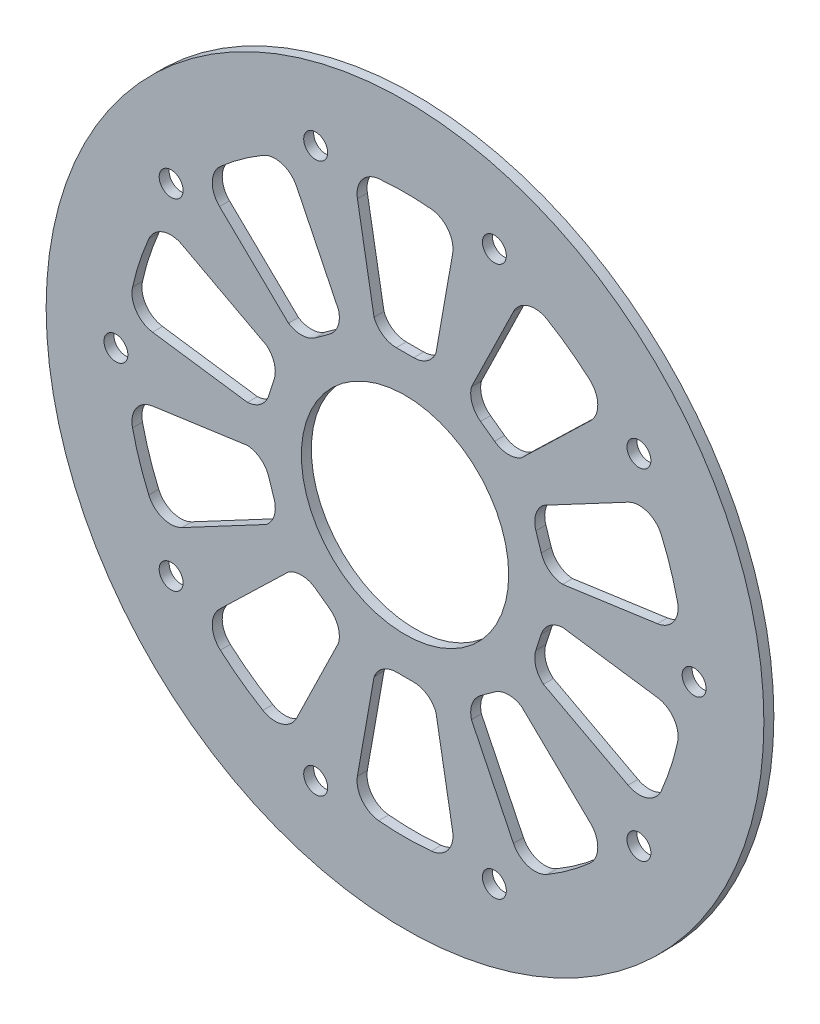
SolidWorks part; units mm, degrees
ref_plane "Ön Düzlem" through (0, 0, 0) normal (0, 0, 1) x (1, 0, 0)
ref_plane "Üst Düzlem" through (0, 0, 0) normal (0, 1, 0) x (1, 0, 0)
ref_plane "Sağ Düzlem" through (0, 0, 0) normal (1, 0, 0) x (0, 0, -1)
sketch "Model" plane through (0, 0, 0) normal (0, 0, 1) x (1, 0, 0)
  line L1 (60.5945, 121.4987) -> (60.8885, 121.3363)
  line L2 (60.8885, 121.3363) -> (61.139, 121.1124)
  line L3 (61.139, 121.1124) -> (61.3334, 120.8385)
  line L4 (61.3334, 120.8385) -> (61.4619, 120.5282)
  line L5 (61.4619, 120.5282) -> (61.5182, 120.197)
  line L6 (61.5182, 120.197) -> (61.4993, 119.8617)
  line L7 (61.4993, 119.8617) -> (61.4063, 119.5389)
  line L8 (61.4063, 119.5389) -> (45.7726, 92.4605)
  line L9 (45.7726, 92.4605) -> (42.0525, 92.3778)
  line L10 (42.0525, 92.3778) -> (41.4785, 90.992)
  line L11 (58.0621, 81.4174) -> (58.9753, 82.6074)
  line L12 (58.9753, 82.6074) -> (57.1868, 85.8705)
  line L13 (57.1868, 85.8705) -> (72.8206, 112.9489)
  line L14 (72.8206, 112.9489) -> (73.0536, 113.1908)
  line L15 (73.0536, 113.1908) -> (73.3346, 113.3748)
  line L16 (73.3346, 113.3748) -> (73.6495, 113.4917)
  line L17 (73.6495, 113.4917) -> (73.9825, 113.5355)
  line L18 (73.9825, 113.5355) -> (74.317, 113.5041)
  line L19 (74.317, 113.5041) -> (74.636, 113.3991)
  line L20 (74.636, 113.3991) -> (74.9237, 113.2258)
  line L21 (74.9237, 113.2258) -> (89.976, 101.6758)
  line L22 (89.976, 101.6758) -> (90.2179, 101.4427)
  line L23 (90.2179, 101.4427) -> (90.4019, 101.1617)
  line L24 (90.4019, 101.1617) -> (90.5188, 100.8468)
  line L25 (90.5188, 100.8468) -> (90.5626, 100.5138)
  line L26 (90.5626, 100.5138) -> (90.5313, 100.1793)
  line L27 (90.5313, 100.1793) -> (90.4263, 99.8603)
  line L28 (90.4263, 99.8603) -> (90.2529, 99.5726)
  line L29 (90.2529, 99.5726) -> (68.1435, 77.4631)
  line L30 (68.1435, 77.4631) -> (64.5287, 78.3461)
  line L31 (64.5287, 78.3461) -> (63.6156, 77.1561)
  line L32 (77.1561, 63.6156) -> (78.3461, 64.5287)
  line L33 (78.3461, 64.5287) -> (77.4631, 68.1435)
  line L34 (77.4631, 68.1435) -> (99.5726, 90.2529)
  line L35 (99.5726, 90.2529) -> (99.8603, 90.4263)
  line L36 (99.8603, 90.4263) -> (100.1793, 90.5313)
  line L37 (100.1793, 90.5313) -> (100.5138, 90.5626)
  line L38 (100.5138, 90.5626) -> (100.8468, 90.5188)
  line L39 (100.8468, 90.5188) -> (101.1617, 90.4019)
  line L40 (101.1617, 90.4019) -> (101.4427, 90.2179)
  line L41 (101.4427, 90.2179) -> (101.6758, 89.976)
  line L42 (101.6758, 89.976) -> (113.2258, 74.9237)
  line L43 (113.2258, 74.9237) -> (113.3991, 74.636)
  line L44 (113.3991, 74.636) -> (113.5041, 74.317)
  line L45 (113.5041, 74.317) -> (113.5355, 73.9825)
  line L46 (113.5355, 73.9825) -> (113.4917, 73.6495)
  line L47 (113.4917, 73.6495) -> (113.3748, 73.3346)
  line L48 (113.3748, 73.3346) -> (113.1908, 73.0536)
  line L49 (113.1908, 73.0536) -> (112.9489, 72.8206)
  line L50 (112.9489, 72.8206) -> (85.8705, 57.1868)
  line L51 (85.8705, 57.1868) -> (82.6074, 58.9753)
  line L52 (82.6074, 58.9753) -> (81.4174, 58.0621)
  line L53 (90.992, 41.4785) -> (92.3778, 42.0525)
  line L54 (92.3778, 42.0525) -> (92.4605, 45.7726)
  line L55 (92.4605, 45.7726) -> (119.5389, 61.4063)
  line L56 (119.5389, 61.4063) -> (119.8617, 61.4993)
  line L57 (119.8617, 61.4993) -> (120.197, 61.5182)
  line L58 (120.197, 61.5182) -> (120.5282, 61.4619)
  line L59 (120.5282, 61.4619) -> (120.8385, 61.3334)
  line L60 (120.8385, 61.3334) -> (121.1124, 61.139)
  line L61 (121.1124, 61.139) -> (121.3363, 60.8885)
  line L62 (121.3363, 60.8885) -> (121.4987, 60.5945)
  line L63 (121.4987, 60.5945) -> (128.7594, 43.0658)
  line L64 (128.7594, 43.0658) -> (128.8524, 42.743)
  line L65 (128.8524, 42.743) -> (128.8712, 42.4076)
  line L66 (128.8712, 42.4076) -> (128.815, 42.0765)
  line L67 (128.815, 42.0765) -> (128.6864, 41.7662)
  line L68 (128.6864, 41.7662) -> (128.492, 41.4922)
  line L69 (128.492, 41.4922) -> (128.2416, 41.2684)
  line L70 (128.2416, 41.2684) -> (127.9476, 41.1059)
  line L71 (127.9476, 41.1059) -> (97.7455, 33.0133)
  line L72 (97.7455, 33.0133) -> (95.0566, 35.5853)
  line L73 (95.0566, 35.5853) -> (93.6707, 35.0113)
  line L74 (98.6269, 16.5147) -> (100.1141, 16.7105)
  line L75 (100.1141, 16.7105) -> (101.1568, 20.2824)
  line L76 (101.1568, 20.2824) -> (131.3588, 28.375)
  line L77 (131.3588, 28.375) -> (131.6947, 28.3813)
  line L78 (131.6947, 28.3813) -> (132.0235, 28.3127)
  line L79 (132.0235, 28.3127) -> (132.3288, 28.1726)
  line L80 (132.3288, 28.1726) -> (132.5953, 27.9682)
  line L81 (132.5953, 27.9682) -> (132.8096, 27.7095)
  line L82 (132.8096, 27.7095) -> (132.9609, 27.4097)
  line L83 (132.9609, 27.4097) -> (133.0418, 27.0836)
  line L84 (133.0418, 27.0836) -> (135.5183, 8.273)
  line L85 (135.5183, 8.273) -> (135.5246, 7.9371)
  line L86 (135.5246, 7.9371) -> (135.4559, 7.6083)
  line L87 (135.4559, 7.6083) -> (135.3159, 7.303)
  line L88 (135.3159, 7.303) -> (135.1114, 7.0365)
  line L89 (135.1114, 7.0365) -> (134.8528, 6.8222)
  line L90 (134.8528, 6.8222) -> (134.5529, 6.6709)
  line L91 (134.5529, 6.6709) -> (134.2269, 6.59)
  line L92 (134.2269, 6.59) -> (102.9594, 6.59)
  line L93 (102.9594, 6.59) -> (101.0278, 9.7704)
  line L94 (101.0278, 9.7704) -> (99.5406, 9.5746)
  line L95 (99.5406, -9.5746) -> (101.0278, -9.7704)
  line L96 (101.0278, -9.7704) -> (102.9594, -6.59)
  line L97 (102.9594, -6.59) -> (134.2269, -6.59)
  line L98 (134.2269, -6.59) -> (134.5529, -6.6709)
  line L99 (134.5529, -6.6709) -> (134.8528, -6.8222)
  line L100 (134.8528, -6.8222) -> (135.1114, -7.0365)
  line L101 (135.1114, -7.0365) -> (135.3159, -7.303)
  line L102 (135.3159, -7.303) -> (135.4559, -7.6083)
  line L103 (135.4559, -7.6083) -> (135.5246, -7.9371)
  line L104 (135.5246, -7.9371) -> (135.5183, -8.273)
  line L105 (135.5183, -8.273) -> (133.0418, -27.0836)
  line L106 (133.0418, -27.0836) -> (132.9609, -27.4097)
  line L107 (132.9609, -27.4097) -> (132.8096, -27.7095)
  line L108 (132.8096, -27.7095) -> (132.5953, -27.9682)
  line L109 (132.5953, -27.9682) -> (132.3288, -28.1726)
  line L110 (132.3288, -28.1726) -> (132.0235, -28.3127)
  line L111 (132.0235, -28.3127) -> (131.6947, -28.3813)
  line L112 (131.6947, -28.3813) -> (131.3588, -28.375)
  line L113 (131.3588, -28.375) -> (101.1568, -20.2824)
  line L114 (101.1568, -20.2824) -> (100.1141, -16.7105)
  line L115 (100.1141, -16.7105) -> (98.6269, -16.5147)
  line L116 (93.6707, -35.0113) -> (95.0566, -35.5853)
  line L117 (95.0566, -35.5853) -> (97.7455, -33.0133)
  line L118 (97.7455, -33.0133) -> (127.9476, -41.1059)
  line L119 (127.9476, -41.1059) -> (128.2416, -41.2684)
  line L120 (128.2416, -41.2684) -> (128.492, -41.4922)
  line L121 (128.492, -41.4922) -> (128.6864, -41.7662)
  line L122 (128.6864, -41.7662) -> (128.815, -42.0765)
  line L123 (128.815, -42.0765) -> (128.8712, -42.4076)
  line L124 (128.8712, -42.4076) -> (128.8524, -42.743)
  line L125 (128.8524, -42.743) -> (128.7594, -43.0658)
  line L126 (128.7594, -43.0658) -> (121.4987, -60.5945)
  line L127 (121.4987, -60.5945) -> (121.3363, -60.8885)
  line L128 (121.3363, -60.8885) -> (121.1124, -61.139)
  line L129 (121.1124, -61.139) -> (120.8385, -61.3334)
  line L130 (120.8385, -61.3334) -> (120.5282, -61.4619)
  line L131 (120.5282, -61.4619) -> (120.197, -61.5182)
  line L132 (120.197, -61.5182) -> (119.8617, -61.4993)
  line L133 (119.8617, -61.4993) -> (119.5389, -61.4063)
  line L134 (119.5389, -61.4063) -> (92.4605, -45.7726)
  line L135 (92.4605, -45.7726) -> (92.3778, -42.0525)
  line L136 (92.3778, -42.0525) -> (90.992, -41.4785)
  line L137 (81.4174, -58.0621) -> (82.6074, -58.9753)
  line L138 (82.6074, -58.9753) -> (85.8705, -57.1868)
  line L139 (85.8705, -57.1868) -> (112.9489, -72.8206)
  line L140 (112.9489, -72.8206) -> (113.1908, -73.0536)
  line L141 (113.1908, -73.0536) -> (113.3748, -73.3346)
  line L142 (113.3748, -73.3346) -> (113.4917, -73.6495)
  line L143 (113.4917, -73.6495) -> (113.5355, -73.9825)
  line L144 (113.5355, -73.9825) -> (113.5041, -74.317)
  line L145 (113.5041, -74.317) -> (113.3991, -74.636)
  line L146 (113.3991, -74.636) -> (113.2258, -74.9237)
  line L147 (113.2258, -74.9237) -> (101.6758, -89.976)
  line L148 (101.6758, -89.976) -> (101.4427, -90.2179)
  line L149 (101.4427, -90.2179) -> (101.1617, -90.4019)
  line L150 (101.1617, -90.4019) -> (100.8468, -90.5188)
  line L151 (100.8468, -90.5188) -> (100.5138, -90.5626)
  line L152 (100.5138, -90.5626) -> (100.1793, -90.5313)
  line L153 (100.1793, -90.5313) -> (99.8603, -90.4263)
  line L154 (99.8603, -90.4263) -> (99.5726, -90.2529)
  line L155 (99.5726, -90.2529) -> (77.4631, -68.1435)
  line L156 (77.4631, -68.1435) -> (78.3461, -64.5287)
  line L157 (78.3461, -64.5287) -> (77.1561, -63.6156)
  line L158 (63.6156, -77.1561) -> (64.5287, -78.3461)
  line L159 (64.5287, -78.3461) -> (68.1435, -77.4631)
  line L160 (68.1435, -77.4631) -> (90.2529, -99.5726)
  line L161 (90.2529, -99.5726) -> (90.4263, -99.8603)
  line L162 (90.4263, -99.8603) -> (90.5313, -100.1793)
  line L163 (90.5313, -100.1793) -> (90.5626, -100.5138)
  line L164 (90.5626, -100.5138) -> (90.5188, -100.8468)
  line L165 (90.5188, -100.8468) -> (90.4019, -101.1617)
  line L166 (90.4019, -101.1617) -> (90.2179, -101.4427)
  line L167 (90.2179, -101.4427) -> (89.976, -101.6758)
  line L168 (89.976, -101.6758) -> (74.9237, -113.2258)
  line L169 (74.9237, -113.2258) -> (74.636, -113.3991)
  line L170 (74.636, -113.3991) -> (74.317, -113.5041)
  line L171 (74.317, -113.5041) -> (73.9825, -113.5355)
  line L172 (73.9825, -113.5355) -> (73.6495, -113.4917)
  line L173 (73.6495, -113.4917) -> (73.3346, -113.3748)
  line L174 (73.3346, -113.3748) -> (73.0536, -113.1908)
  line L175 (73.0536, -113.1908) -> (72.8206, -112.9489)
  line L176 (72.8206, -112.9489) -> (57.1868, -85.8705)
  line L177 (57.1868, -85.8705) -> (58.9753, -82.6074)
  line L178 (58.9753, -82.6074) -> (58.0621, -81.4174)
  line L179 (41.4785, -90.992) -> (42.0525, -92.3778)
  line L180 (42.0525, -92.3778) -> (45.7726, -92.4605)
  line L181 (45.7726, -92.4605) -> (61.4063, -119.5389)
  line L182 (61.4063, -119.5389) -> (61.4993, -119.8617)
  line L183 (61.4993, -119.8617) -> (61.5182, -120.197)
  line L184 (61.5182, -120.197) -> (61.4619, -120.5282)
  line L185 (61.4619, -120.5282) -> (61.3334, -120.8385)
  line L186 (61.3334, -120.8385) -> (61.139, -121.1124)
  line L187 (61.139, -121.1124) -> (60.8885, -121.3363)
  line L188 (60.8885, -121.3363) -> (60.5945, -121.4987)
  line L189 (60.5945, -121.4987) -> (43.0658, -128.7594)
  line L190 (43.0658, -128.7594) -> (42.743, -128.8524)
  line L191 (42.743, -128.8524) -> (42.4076, -128.8712)
  line L192 (42.4076, -128.8712) -> (42.0765, -128.815)
  line L193 (42.0765, -128.815) -> (41.7662, -128.6864)
  line L194 (41.7662, -128.6864) -> (41.4922, -128.492)
  line L195 (41.4922, -128.492) -> (41.2684, -128.2416)
  line L196 (41.2684, -128.2416) -> (41.1059, -127.9476)
  line L197 (41.1059, -127.9476) -> (33.0133, -97.7455)
  line L198 (33.0133, -97.7455) -> (35.5853, -95.0566)
  line L199 (35.5853, -95.0566) -> (35.0113, -93.6707)
  line L200 (16.5147, -98.6269) -> (16.7105, -100.1141)
  line L201 (16.7105, -100.1141) -> (20.2824, -101.1568)
  line L202 (20.2824, -101.1568) -> (28.375, -131.3588)
  line L203 (28.375, -131.3588) -> (28.3813, -131.6947)
  line L204 (28.3813, -131.6947) -> (28.3127, -132.0235)
  line L205 (28.3127, -132.0235) -> (28.1726, -132.3288)
  line L206 (28.1726, -132.3288) -> (27.9682, -132.5953)
  line L207 (27.9682, -132.5953) -> (27.7095, -132.8096)
  line L208 (27.7095, -132.8096) -> (27.4097, -132.9609)
  line L209 (27.4097, -132.9609) -> (27.0836, -133.0418)
  line L210 (27.0836, -133.0418) -> (8.273, -135.5183)
  line L211 (8.273, -135.5183) -> (7.9371, -135.5246)
  line L212 (7.9371, -135.5246) -> (7.6083, -135.4559)
  line L213 (7.6083, -135.4559) -> (7.303, -135.3159)
  line L214 (7.303, -135.3159) -> (7.0365, -135.1114)
  line L215 (7.0365, -135.1114) -> (6.8222, -134.8528)
  line L216 (6.8222, -134.8528) -> (6.6709, -134.5529)
  line L217 (6.6709, -134.5529) -> (6.59, -134.2269)
  line L218 (6.59, -134.2269) -> (6.59, -102.9594)
  line L219 (6.59, -102.9594) -> (9.7704, -101.0278)
  line L220 (9.7704, -101.0278) -> (9.5746, -99.5406)
  line L221 (-9.5746, -99.5406) -> (-9.7704, -101.0278)
  line L222 (-9.7704, -101.0278) -> (-6.59, -102.9594)
  line L223 (-6.59, -102.9594) -> (-6.59, -134.2269)
  line L224 (-6.59, -134.2269) -> (-6.6709, -134.5529)
  line L225 (-6.6709, -134.5529) -> (-6.8222, -134.8528)
  line L226 (-6.8222, -134.8528) -> (-7.0365, -135.1114)
  line L227 (-7.0365, -135.1114) -> (-7.303, -135.3159)
  line L228 (-7.303, -135.3159) -> (-7.6083, -135.4559)
  line L229 (-7.6083, -135.4559) -> (-7.9371, -135.5246)
  line L230 (-7.9371, -135.5246) -> (-8.273, -135.5183)
  line L231 (-8.273, -135.5183) -> (-27.0836, -133.0418)
  line L232 (-27.0836, -133.0418) -> (-27.4097, -132.9609)
  line L233 (-27.4097, -132.9609) -> (-27.7095, -132.8096)
  line L234 (-27.7095, -132.8096) -> (-27.9682, -132.5953)
  line L235 (-27.9682, -132.5953) -> (-28.1726, -132.3288)
  line L236 (-28.1726, -132.3288) -> (-28.3127, -132.0235)
  line L237 (-28.3127, -132.0235) -> (-28.3813, -131.6947)
  line L238 (-28.3813, -131.6947) -> (-28.375, -131.3588)
  line L239 (-28.375, -131.3588) -> (-20.2824, -101.1568)
  line L240 (-20.2824, -101.1568) -> (-16.7105, -100.1141)
  line L241 (-16.7105, -100.1141) -> (-16.5147, -98.6269)
  line L242 (-35.0113, -93.6707) -> (-35.5853, -95.0566)
  line L243 (-35.5853, -95.0566) -> (-33.0133, -97.7455)
  line L244 (-33.0133, -97.7455) -> (-41.1059, -127.9476)
  line L245 (-41.1059, -127.9476) -> (-41.2684, -128.2416)
  line L246 (-41.2684, -128.2416) -> (-41.4922, -128.492)
  line L247 (-41.4922, -128.492) -> (-41.7662, -128.6864)
  line L248 (-41.7662, -128.6864) -> (-42.0765, -128.815)
  line L249 (-42.0765, -128.815) -> (-42.4076, -128.8712)
  line L250 (-42.4076, -128.8712) -> (-42.743, -128.8524)
  line L251 (-42.743, -128.8524) -> (-43.0658, -128.7594)
  line L252 (-43.0658, -128.7594) -> (-60.5945, -121.4987)
  line L253 (-60.5945, -121.4987) -> (-60.8885, -121.3363)
  line L254 (-60.8885, -121.3363) -> (-61.139, -121.1124)
  line L255 (-61.139, -121.1124) -> (-61.3334, -120.8385)
  line L256 (-61.3334, -120.8385) -> (-61.4619, -120.5282)
  line L257 (-61.4619, -120.5282) -> (-61.5182, -120.197)
  line L258 (-61.5182, -120.197) -> (-61.4993, -119.8617)
  line L259 (-61.4993, -119.8617) -> (-61.4063, -119.5389)
  line L260 (-61.4063, -119.5389) -> (-45.7726, -92.4605)
  line L261 (-45.7726, -92.4605) -> (-42.0525, -92.3778)
  line L262 (-42.0525, -92.3778) -> (-41.4785, -90.992)
  line L263 (-58.0621, -81.4174) -> (-58.9753, -82.6074)
  line L264 (-58.9753, -82.6074) -> (-57.1868, -85.8705)
  line L265 (-57.1868, -85.8705) -> (-72.8206, -112.9489)
  line L266 (-72.8206, -112.9489) -> (-73.0536, -113.1908)
  line L267 (-73.0536, -113.1908) -> (-73.3346, -113.3748)
  line L268 (-73.3346, -113.3748) -> (-73.6495, -113.4917)
  line L269 (-73.6495, -113.4917) -> (-73.9825, -113.5355)
  line L270 (-73.9825, -113.5355) -> (-74.317, -113.5041)
  line L271 (-74.317, -113.5041) -> (-74.636, -113.3991)
  line L272 (-74.636, -113.3991) -> (-74.9237, -113.2258)
  line L273 (-74.9237, -113.2258) -> (-89.976, -101.6758)
  line L274 (-89.976, -101.6758) -> (-90.2179, -101.4427)
  line L275 (-90.2179, -101.4427) -> (-90.4019, -101.1617)
  line L276 (-90.4019, -101.1617) -> (-90.5188, -100.8468)
  line L277 (-90.5188, -100.8468) -> (-90.5626, -100.5138)
  line L278 (-90.5626, -100.5138) -> (-90.5313, -100.1793)
  line L279 (-90.5313, -100.1793) -> (-90.4263, -99.8603)
  line L280 (-90.4263, -99.8603) -> (-90.2529, -99.5726)
  line L281 (-90.2529, -99.5726) -> (-68.1435, -77.4631)
  line L282 (-68.1435, -77.4631) -> (-64.5287, -78.3461)
  line L283 (-64.5287, -78.3461) -> (-63.6156, -77.1561)
  line L284 (-77.1561, -63.6156) -> (-78.3461, -64.5287)
  line L285 (-78.3461, -64.5287) -> (-77.4631, -68.1435)
  line L286 (-77.4631, -68.1435) -> (-99.5726, -90.2529)
  line L287 (-99.5726, -90.2529) -> (-99.8603, -90.4263)
  line L288 (-99.8603, -90.4263) -> (-100.1793, -90.5313)
  line L289 (-100.1793, -90.5313) -> (-100.5138, -90.5626)
  line L290 (-100.5138, -90.5626) -> (-100.8468, -90.5188)
  line L291 (-100.8468, -90.5188) -> (-101.1617, -90.4019)
  line L292 (-101.1617, -90.4019) -> (-101.4427, -90.2179)
  line L293 (-101.4427, -90.2179) -> (-101.6758, -89.976)
  line L294 (-101.6758, -89.976) -> (-113.2258, -74.9237)
  line L295 (-113.2258, -74.9237) -> (-113.3991, -74.636)
  line L296 (-113.3991, -74.636) -> (-113.5041, -74.317)
  line L297 (-113.5041, -74.317) -> (-113.5355, -73.9825)
  line L298 (-113.5355, -73.9825) -> (-113.4917, -73.6495)
  line L299 (-113.4917, -73.6495) -> (-113.3748, -73.3346)
  line L300 (-113.3748, -73.3346) -> (-113.1908, -73.0536)
  line L301 (-113.1908, -73.0536) -> (-112.9489, -72.8206)
  line L302 (-112.9489, -72.8206) -> (-85.8705, -57.1868)
  line L303 (-85.8705, -57.1868) -> (-82.6074, -58.9753)
  line L304 (-82.6074, -58.9753) -> (-81.4174, -58.0621)
  line L305 (-90.992, -41.4785) -> (-92.3778, -42.0525)
  line L306 (-92.3778, -42.0525) -> (-92.4605, -45.7726)
  line L307 (-92.4605, -45.7726) -> (-119.5389, -61.4063)
  line L308 (-119.5389, -61.4063) -> (-119.8617, -61.4993)
  line L309 (-119.8617, -61.4993) -> (-120.197, -61.5182)
  line L310 (-120.197, -61.5182) -> (-120.5282, -61.4619)
  line L311 (-120.5282, -61.4619) -> (-120.8385, -61.3334)
  line L312 (-120.8385, -61.3334) -> (-121.1124, -61.139)
  line L313 (-121.1124, -61.139) -> (-121.3363, -60.8885)
  line L314 (-121.3363, -60.8885) -> (-121.4987, -60.5945)
  line L315 (-121.4987, -60.5945) -> (-128.7594, -43.0658)
  line L316 (-128.7594, -43.0658) -> (-128.8524, -42.743)
  line L317 (-128.8524, -42.743) -> (-128.8712, -42.4076)
  line L318 (-128.8712, -42.4076) -> (-128.815, -42.0765)
  line L319 (-128.815, -42.0765) -> (-128.6864, -41.7662)
  line L320 (-128.6864, -41.7662) -> (-128.492, -41.4922)
  line L321 (-128.492, -41.4922) -> (-128.2416, -41.2684)
  line L322 (-128.2416, -41.2684) -> (-127.9476, -41.1059)
  line L323 (-127.9476, -41.1059) -> (-97.7455, -33.0133)
  line L324 (-97.7455, -33.0133) -> (-95.0566, -35.5853)
  line L325 (-95.0566, -35.5853) -> (-93.6707, -35.0113)
  line L326 (-98.6269, -16.5147) -> (-100.1141, -16.7105)
  line L327 (-100.1141, -16.7105) -> (-101.1568, -20.2824)
  line L328 (-101.1568, -20.2824) -> (-131.3588, -28.375)
  line L329 (-131.3588, -28.375) -> (-131.6947, -28.3813)
  line L330 (-131.6947, -28.3813) -> (-132.0235, -28.3127)
  line L331 (-132.0235, -28.3127) -> (-132.3288, -28.1726)
  line L332 (-132.3288, -28.1726) -> (-132.5953, -27.9682)
  line L333 (-132.5953, -27.9682) -> (-132.8096, -27.7095)
  line L334 (-132.8096, -27.7095) -> (-132.9609, -27.4097)
  line L335 (-132.9609, -27.4097) -> (-133.0418, -27.0836)
  line L336 (-133.0418, -27.0836) -> (-135.5183, -8.273)
  line L337 (-135.5183, -8.273) -> (-135.5246, -7.9371)
  line L338 (-135.5246, -7.9371) -> (-135.4559, -7.6083)
  line L339 (-135.4559, -7.6083) -> (-135.3159, -7.303)
  line L340 (-135.3159, -7.303) -> (-135.1114, -7.0365)
  line L341 (-135.1114, -7.0365) -> (-134.8528, -6.8222)
  line L342 (-134.8528, -6.8222) -> (-134.5529, -6.6709)
  line L343 (-134.5529, -6.6709) -> (-134.2269, -6.59)
  line L344 (-134.2269, -6.59) -> (-102.9594, -6.59)
  line L345 (-102.9594, -6.59) -> (-101.0278, -9.7704)
  line L346 (-101.0278, -9.7704) -> (-99.5406, -9.5746)
  line L347 (-99.5406, 9.5746) -> (-101.0278, 9.7704)
  line L348 (-101.0278, 9.7704) -> (-102.9594, 6.59)
  line L349 (-102.9594, 6.59) -> (-134.2269, 6.59)
  line L350 (-134.2269, 6.59) -> (-134.5529, 6.6709)
  line L351 (-134.5529, 6.6709) -> (-134.8528, 6.8222)
  line L352 (-134.8528, 6.8222) -> (-135.1114, 7.0365)
  line L353 (-135.1114, 7.0365) -> (-135.3159, 7.303)
  line L354 (-135.3159, 7.303) -> (-135.4559, 7.6083)
  line L355 (-135.4559, 7.6083) -> (-135.5246, 7.9371)
  line L356 (-135.5246, 7.9371) -> (-135.5183, 8.273)
  line L357 (-135.5183, 8.273) -> (-133.0418, 27.0836)
  line L358 (-133.0418, 27.0836) -> (-132.9609, 27.4097)
  line L359 (-132.9609, 27.4097) -> (-132.8096, 27.7095)
  line L360 (-132.8096, 27.7095) -> (-132.5953, 27.9682)
  line L361 (-132.5953, 27.9682) -> (-132.3288, 28.1726)
  line L362 (-132.3288, 28.1726) -> (-132.0235, 28.3127)
  line L363 (-132.0235, 28.3127) -> (-131.6947, 28.3813)
  line L364 (-131.6947, 28.3813) -> (-131.3588, 28.375)
  line L365 (-131.3588, 28.375) -> (-101.1568, 20.2824)
  line L366 (-101.1568, 20.2824) -> (-100.1141, 16.7105)
  line L367 (-100.1141, 16.7105) -> (-98.6269, 16.5147)
  line L368 (-93.6707, 35.0113) -> (-95.0566, 35.5853)
  line L369 (-95.0566, 35.5853) -> (-97.7455, 33.0133)
  line L370 (-97.7455, 33.0133) -> (-127.9476, 41.1059)
  line L371 (-127.9476, 41.1059) -> (-128.2416, 41.2684)
  line L372 (-128.2416, 41.2684) -> (-128.492, 41.4922)
  line L373 (-128.492, 41.4922) -> (-128.6864, 41.7662)
  line L374 (-128.6864, 41.7662) -> (-128.815, 42.0765)
  line L375 (-128.815, 42.0765) -> (-128.8712, 42.4076)
  line L376 (-128.8712, 42.4076) -> (-128.8524, 42.743)
  line L377 (-128.8524, 42.743) -> (-128.7594, 43.0658)
  line L378 (-128.7594, 43.0658) -> (-121.4987, 60.5945)
  line L379 (-121.4987, 60.5945) -> (-121.3363, 60.8885)
  line L380 (-121.3363, 60.8885) -> (-121.1124, 61.139)
  line L381 (-121.1124, 61.139) -> (-120.8385, 61.3334)
  line L382 (-120.8385, 61.3334) -> (-120.5282, 61.4619)
  line L383 (-120.5282, 61.4619) -> (-120.197, 61.5182)
  line L384 (-120.197, 61.5182) -> (-119.8617, 61.4993)
  line L385 (-119.8617, 61.4993) -> (-119.5389, 61.4063)
  line L386 (-119.5389, 61.4063) -> (-92.4605, 45.7726)
  line L387 (-92.4605, 45.7726) -> (-92.3778, 42.0525)
  line L388 (-92.3778, 42.0525) -> (-90.992, 41.4785)
  line L389 (-81.4174, 58.0621) -> (-82.6074, 58.9753)
  line L390 (-82.6074, 58.9753) -> (-85.8705, 57.1868)
  line L391 (-85.8705, 57.1868) -> (-112.9489, 72.8206)
  line L392 (-112.9489, 72.8206) -> (-113.1908, 73.0536)
  line L393 (-113.1908, 73.0536) -> (-113.3748, 73.3346)
  line L394 (-113.3748, 73.3346) -> (-113.4917, 73.6495)
  line L395 (-113.4917, 73.6495) -> (-113.5355, 73.9825)
  line L396 (-113.5355, 73.9825) -> (-113.5041, 74.317)
  line L397 (-113.5041, 74.317) -> (-113.3991, 74.636)
  line L398 (-113.3991, 74.636) -> (-113.2258, 74.9237)
  line L399 (-113.2258, 74.9237) -> (-101.6758, 89.976)
  line L400 (-101.6758, 89.976) -> (-101.4427, 90.2179)
  line L401 (-101.4427, 90.2179) -> (-101.1617, 90.4019)
  line L402 (-101.1617, 90.4019) -> (-100.8468, 90.5188)
  line L403 (-100.8468, 90.5188) -> (-100.5138, 90.5626)
  line L404 (-100.5138, 90.5626) -> (-100.1793, 90.5313)
  line L405 (-100.1793, 90.5313) -> (-99.8603, 90.4263)
  line L406 (-99.8603, 90.4263) -> (-99.5726, 90.2529)
  line L407 (-99.5726, 90.2529) -> (-77.4631, 68.1435)
  line L408 (-77.4631, 68.1435) -> (-78.3461, 64.5287)
  line L409 (-78.3461, 64.5287) -> (-77.1561, 63.6156)
  line L410 (-63.6156, 77.1561) -> (-64.5287, 78.3461)
  line L411 (-64.5287, 78.3461) -> (-68.1435, 77.4631)
  line L412 (-68.1435, 77.4631) -> (-90.2529, 99.5726)
  line L413 (-90.2529, 99.5726) -> (-90.4263, 99.8603)
  line L414 (-90.4263, 99.8603) -> (-90.5313, 100.1793)
  line L415 (-90.5313, 100.1793) -> (-90.5626, 100.5138)
  line L416 (-90.5626, 100.5138) -> (-90.5188, 100.8468)
  line L417 (-90.5188, 100.8468) -> (-90.4019, 101.1617)
  line L418 (-90.4019, 101.1617) -> (-90.2179, 101.4427)
  line L419 (-90.2179, 101.4427) -> (-89.976, 101.6758)
  line L420 (-89.976, 101.6758) -> (-74.9237, 113.2258)
  line L421 (-74.9237, 113.2258) -> (-74.636, 113.3991)
  line L422 (-74.636, 113.3991) -> (-74.317, 113.5041)
  line L423 (-74.317, 113.5041) -> (-73.9825, 113.5355)
  line L424 (-73.9825, 113.5355) -> (-73.6495, 113.4917)
  line L425 (-73.6495, 113.4917) -> (-73.3346, 113.3748)
  line L426 (-73.3346, 113.3748) -> (-73.0536, 113.1908)
  line L427 (-73.0536, 113.1908) -> (-72.8206, 112.9489)
  line L428 (-72.8206, 112.9489) -> (-57.1868, 85.8705)
  line L429 (-57.1868, 85.8705) -> (-58.9753, 82.6074)
  line L430 (-58.9753, 82.6074) -> (-58.0621, 81.4174)
  line L431 (-41.4785, 90.992) -> (-42.0525, 92.3778)
  line L432 (-42.0525, 92.3778) -> (-45.7726, 92.4605)
  line L433 (-45.7726, 92.4605) -> (-61.4063, 119.5389)
  line L434 (-61.4063, 119.5389) -> (-61.4993, 119.8617)
  line L435 (-61.4993, 119.8617) -> (-61.5182, 120.197)
  line L436 (-61.5182, 120.197) -> (-61.4619, 120.5282)
  line L437 (-61.4619, 120.5282) -> (-61.3334, 120.8385)
  line L438 (-61.3334, 120.8385) -> (-61.139, 121.1124)
  line L439 (-61.139, 121.1124) -> (-60.8885, 121.3363)
  line L440 (-60.8885, 121.3363) -> (-60.5945, 121.4987)
  line L441 (-60.5945, 121.4987) -> (-43.0658, 128.7594)
  line L442 (-43.0658, 128.7594) -> (-42.743, 128.8524)
  line L443 (-42.743, 128.8524) -> (-42.4076, 128.8712)
  line L444 (-42.4076, 128.8712) -> (-42.0765, 128.815)
  line L445 (-42.0765, 128.815) -> (-41.7662, 128.6864)
  line L446 (-41.7662, 128.6864) -> (-41.4922, 128.492)
  line L447 (-41.4922, 128.492) -> (-41.2684, 128.2416)
  line L448 (-41.2684, 128.2416) -> (-41.1059, 127.9476)
  line L449 (-41.1059, 127.9476) -> (-33.0133, 97.7455)
  line L450 (-33.0133, 97.7455) -> (-35.5853, 95.0566)
  line L451 (-35.5853, 95.0566) -> (-35.0113, 93.6707)
  line L452 (-16.5147, 98.6269) -> (-16.7105, 100.1141)
  line L453 (-16.7105, 100.1141) -> (-20.2824, 101.1568)
  line L454 (-20.2824, 101.1568) -> (-28.375, 131.3588)
  line L455 (-28.375, 131.3588) -> (-28.3813, 131.6947)
  line L456 (-28.3813, 131.6947) -> (-28.3127, 132.0235)
  line L457 (-28.3127, 132.0235) -> (-28.1726, 132.3288)
  line L458 (-28.1726, 132.3288) -> (-27.9682, 132.5953)
  line L459 (-27.9682, 132.5953) -> (-27.7095, 132.8096)
  line L460 (-27.7095, 132.8096) -> (-27.4097, 132.9609)
  line L461 (-27.4097, 132.9609) -> (-27.0836, 133.0418)
  line L462 (-27.0836, 133.0418) -> (-8.273, 135.5183)
  line L463 (-8.273, 135.5183) -> (-7.9371, 135.5246)
  line L464 (-7.9371, 135.5246) -> (-7.6083, 135.4559)
  line L465 (-7.6083, 135.4559) -> (-7.303, 135.3159)
  line L466 (-7.303, 135.3159) -> (-7.0365, 135.1114)
  line L467 (-7.0365, 135.1114) -> (-6.8222, 134.8528)
  line L468 (-6.8222, 134.8528) -> (-6.6709, 134.5529)
  line L469 (-6.6709, 134.5529) -> (-6.59, 134.2269)
  line L470 (-6.59, 134.2269) -> (-6.59, 102.9594)
  line L471 (-6.59, 102.9594) -> (-9.7704, 101.0278)
  line L472 (-9.7704, 101.0278) -> (-9.5746, 99.5406)
  line L473 (9.5746, 99.5406) -> (9.7704, 101.0278)
  line L474 (9.7704, 101.0278) -> (6.59, 102.9594)
  line L475 (6.59, 102.9594) -> (6.59, 134.2269)
  line L476 (6.59, 134.2269) -> (6.6709, 134.5529)
  line L477 (6.6709, 134.5529) -> (6.8222, 134.8528)
  line L478 (6.8222, 134.8528) -> (7.0365, 135.1114)
  line L479 (7.0365, 135.1114) -> (7.303, 135.3159)
  line L480 (7.303, 135.3159) -> (7.6083, 135.4559)
  line L481 (7.6083, 135.4559) -> (7.9371, 135.5246)
  line L482 (7.9371, 135.5246) -> (8.273, 135.5183)
  line L483 (8.273, 135.5183) -> (27.0836, 133.0418)
  line L484 (27.0836, 133.0418) -> (27.4097, 132.9609)
  line L485 (27.4097, 132.9609) -> (27.7095, 132.8096)
  line L486 (27.7095, 132.8096) -> (27.9682, 132.5953)
  line L487 (27.9682, 132.5953) -> (28.1726, 132.3288)
  line L488 (28.1726, 132.3288) -> (28.3127, 132.0235)
  line L489 (28.3127, 132.0235) -> (28.3813, 131.6947)
  line L490 (28.3813, 131.6947) -> (28.375, 131.3588)
  line L491 (28.375, 131.3588) -> (20.2824, 101.1568)
  line L492 (20.2824, 101.1568) -> (16.7105, 100.1141)
  line L493 (16.7105, 100.1141) -> (16.5147, 98.6269)
  line L494 (35.0113, 93.6707) -> (35.5853, 95.0566)
  line L495 (35.5853, 95.0566) -> (33.0133, 97.7455)
  line L496 (33.0133, 97.7455) -> (41.1059, 127.9476)
  line L497 (41.1059, 127.9476) -> (41.2684, 128.2416)
  line L498 (41.2684, 128.2416) -> (41.4922, 128.492)
  line L499 (41.4922, 128.492) -> (41.7662, 128.6864)
  line L500 (41.7662, 128.6864) -> (42.0765, 128.815)
  line L501 (42.0765, 128.815) -> (42.4076, 128.8712)
  line L502 (42.4076, 128.8712) -> (42.743, 128.8524)
  line L503 (42.743, 128.8524) -> (43.0658, 128.7594)
  line L504 (43.0658, 128.7594) -> (60.5945, 121.4987)
  line L508 (27.7776, -94.5021) -> (26.5086, -90.1848)
  line L509 (2.6574, -93.9624) -> (2.7847, -98.4606)
  line L510 (-27.7776, 94.5021) -> (-26.5086, 90.1848)
  line L511 (-2.6574, 93.9624) -> (-2.7847, 98.4606)
  line L512 (94.5021, 27.7776) -> (90.1848, 26.5086)
  line L513 (93.9624, 2.6574) -> (98.4606, 2.7847)
  line L514 (-94.5021, -27.7776) -> (-90.1848, -26.5086)
  line L515 (-93.9624, -2.6574) -> (-98.4606, -2.7847)
  line L516 (55.6209, -81.2931) -> (53.0798, -77.5792)
  line L517 (31.5634, -88.5424) -> (33.0744, -92.7811)
  line L518 (-55.6209, 81.2931) -> (-53.0798, 77.5792)
  line L519 (-31.5634, 88.5424) -> (-33.0744, 92.7811)
  line L520 (81.2931, 55.6209) -> (77.5792, 53.0798)
  line L521 (88.5424, 31.5634) -> (92.7811, 33.0744)
  line L522 (-81.2931, -55.6209) -> (-77.5792, -53.0798)
  line L523 (-88.5424, -31.5634) -> (-92.7811, -33.0744)
  line L524 (78.0195, -60.1265) -> (74.4552, -57.3796)
  line L525 (57.3796, -74.4552) -> (60.1265, -78.0195)
  line L526 (-78.0195, 60.1265) -> (-74.4552, 57.3796)
  line L527 (-57.3796, 74.4552) -> (-60.1265, 78.0195)
  line L528 (60.1265, 78.0195) -> (57.3796, 74.4552)
  line L529 (74.4552, 57.3796) -> (78.0195, 60.1265)
  line L530 (-60.1265, -78.0195) -> (-57.3796, -74.4552)
  line L531 (-74.4552, -57.3796) -> (-78.0195, -60.1265)
  line L532 (92.7811, -33.0744) -> (88.5424, -31.5634)
  line L533 (77.5792, -53.0798) -> (81.2931, -55.6209)
  line L534 (-92.7811, 33.0744) -> (-88.5424, 31.5634)
  line L535 (-77.5792, 53.0798) -> (-81.2931, 55.6209)
  line L536 (33.0744, 92.7811) -> (31.5634, 88.5424)
  line L537 (53.0798, 77.5792) -> (55.6209, 81.2931)
  line L538 (-33.0744, -92.7811) -> (-31.5634, -88.5424)
  line L539 (-53.0798, -77.5792) -> (-55.6209, -81.2931)
  line L540 (98.4606, -2.7847) -> (93.9624, -2.6574)
  line L541 (90.1848, -26.5086) -> (94.5021, -27.7776)
  line L542 (-98.4606, 2.7847) -> (-93.9624, 2.6574)
  line L543 (-90.1848, 26.5086) -> (-94.5021, 27.7776)
  line L544 (2.7847, 98.4606) -> (2.6574, 93.9624)
  line L545 (26.5086, 90.1848) -> (27.7776, 94.5021)
  line L546 (-2.7847, -98.4606) -> (-2.6574, -93.9624)
  line L547 (-26.5086, -90.1848) -> (-27.7776, -94.5021)
  line L556 (-7.7629, 39.0257) -> (-11.9363, 62.6943)
  line L557 (7.7629, 39.0257) -> (11.9363, 62.6943)
  line L558 (16.6584, 36.1354) -> (27.1941, 57.7368)
  line L559 (29.2191, 27.0095) -> (46.5075, 43.7048)
  line L560 (22.4686, 27.2158) -> (18.9406, 29.779)
  line L561 (34.7168, 19.4426) -> (55.9373, 30.7257)
  line L562 (39.5145, 4.6766) -> (63.3144, 8.0215)
  line L563 (34.1745, 8.8113) -> (32.8269, 12.9587)
  line L564 (39.5145, -4.6766) -> (63.3144, -8.0215)
  line L565 (34.7168, -19.4426) -> (55.9373, -30.7257)
  line L566 (32.8269, -12.9587) -> (34.1745, -8.8113)
  line L567 (29.2191, -27.0095) -> (46.5075, -43.7048)
  line L568 (16.6584, -36.1354) -> (27.1941, -57.7368)
  line L569 (18.9406, -29.779) -> (22.4686, -27.2158)
  line L570 (7.7629, -39.0257) -> (11.9363, -62.6943)
  line L571 (-7.7629, -39.0257) -> (-11.9363, -62.6943)
  line L572 (-2.1804, -35.2247) -> (2.1804, -35.2247)
  line L573 (-16.6584, -36.1354) -> (-27.1941, -57.7368)
  line L574 (-29.2191, -27.0095) -> (-46.5075, -43.7048)
  line L575 (-22.4686, -27.2158) -> (-18.9406, -29.779)
  line L578 (-34.7168, -19.4426) -> (-55.9373, -30.7257)
  line L579 (-39.5145, -4.6766) -> (-63.3144, -8.0215)
  line L580 (2.1804, 35.2247) -> (-2.1804, 35.2247)
  line L581 (-34.1745, -8.8113) -> (-32.8269, -12.9587)
  line L582 (-39.5145, 4.6766) -> (-63.3144, 8.0215)
  line L583 (-34.7168, 19.4426) -> (-55.9373, 30.7257)
  line L584 (-32.8269, 12.9587) -> (-34.1745, 8.8113)
  line L585 (-29.2191, 27.0095) -> (-46.5075, 43.7048)
  line L586 (-16.6584, 36.1354) -> (-27.1941, 57.7368)
  line L587 (-18.9406, 29.779) -> (-22.4686, 27.2158)
  arc A0 (145, 0) -> (64.7137, 129.758) centre (0, 0) ccw
  arc A1 (58.0621, 81.4174) -> (41.4785, 90.992) centre (0, 0) ccw
  arc A2 (77.1561, 63.6156) -> (63.6156, 77.1561) centre (0, 0) ccw
  arc A3 (90.992, 41.4785) -> (81.4174, 58.0621) centre (0, 0) ccw
  arc A4 (98.6269, 16.5147) -> (93.6707, 35.0113) centre (0, 0) ccw
  arc A5 (99.5406, -9.5746) -> (99.5406, 9.5746) centre (0, 0) ccw
  arc A6 (93.6707, -35.0113) -> (98.6269, -16.5147) centre (0, 0) ccw
  arc A7 (81.4174, -58.0621) -> (90.992, -41.4785) centre (0, 0) ccw
  arc A8 (63.6156, -77.1561) -> (77.1561, -63.6156) centre (0, 0) ccw
  arc A9 (41.4785, -90.992) -> (58.0621, -81.4174) centre (0, 0) ccw
  arc A10 (16.5147, -98.6269) -> (35.0113, -93.6707) centre (0, 0) ccw
  arc A11 (-9.5746, -99.5406) -> (9.5746, -99.5406) centre (0, 0) ccw
  arc A12 (-35.0113, -93.6707) -> (-16.5147, -98.6269) centre (0, 0) ccw
  arc A13 (-58.0621, -81.4174) -> (-41.4785, -90.992) centre (0, 0) ccw
  arc A14 (-77.1561, -63.6156) -> (-63.6156, -77.1561) centre (0, 0) ccw
  arc A15 (-90.992, -41.4785) -> (-81.4174, -58.0621) centre (0, 0) ccw
  arc A16 (-98.6269, -16.5147) -> (-93.6707, -35.0113) centre (0, 0) ccw
  arc A17 (-99.5406, 9.5746) -> (-99.5406, -9.5746) centre (0, 0) ccw
  arc A18 (-93.6707, 35.0113) -> (-98.6269, 16.5147) centre (0, 0) ccw
  arc A19 (-81.4174, 58.0621) -> (-90.992, 41.4785) centre (0, 0) ccw
  arc A20 (-63.6156, 77.1561) -> (-77.1561, 63.6156) centre (0, 0) ccw
  arc A21 (-41.4785, 90.992) -> (-58.0621, 81.4174) centre (0, 0) ccw
  arc A22 (-16.5147, 98.6269) -> (-35.0113, 93.6707) centre (0, 0) ccw
  arc A23 (9.5746, 99.5406) -> (-9.5746, 99.5406) centre (0, 0) ccw
  arc A24 (35.0113, 93.6707) -> (16.5147, 98.6269) centre (0, 0) ccw
  arc A25 (64.7137, 129.758) -> (145, 0) centre (0, 0) ccw
  arc A26 (94, 0) -> (-94, 0) centre (0, 0) ccw
  arc A28 (-94, 0) -> (94, 0) centre (0, 0) ccw
  arc A29 (2.7847, -98.4606) -> (27.7776, -94.5021) centre (0, 0) ccw
  arc A30 (2.6574, -93.9624) -> (26.5086, -90.1848) centre (0, 0) ccw
  arc A31 (-2.7847, 98.4606) -> (-27.7776, 94.5021) centre (0, 0) ccw
  arc A32 (-2.6574, 93.9624) -> (-26.5086, 90.1848) centre (0, 0) ccw
  arc A33 (98.4606, 2.7847) -> (94.5021, 27.7776) centre (0, 0) ccw
  arc A34 (93.9624, 2.6574) -> (90.1848, 26.5086) centre (0, 0) ccw
  arc A35 (-98.4606, -2.7847) -> (-94.5021, -27.7776) centre (0, 0) ccw
  arc A36 (-93.9624, -2.6574) -> (-90.1848, -26.5086) centre (0, 0) ccw
  arc A37 (33.0744, -92.7811) -> (55.6209, -81.2931) centre (0, 0) ccw
  arc A38 (31.5634, -88.5424) -> (53.0798, -77.5792) centre (0, 0) ccw
  arc A39 (-33.0744, 92.7811) -> (-55.6209, 81.2931) centre (0, 0) ccw
  arc A40 (-31.5634, 88.5424) -> (-53.0798, 77.5792) centre (0, 0) ccw
  arc A41 (92.7811, 33.0744) -> (81.2931, 55.6209) centre (0, 0) ccw
  arc A42 (88.5424, 31.5634) -> (77.5792, 53.0798) centre (0, 0) ccw
  arc A43 (-92.7811, -33.0744) -> (-81.2931, -55.6209) centre (0, 0) ccw
  arc A44 (-88.5424, -31.5634) -> (-77.5792, -53.0798) centre (0, 0) ccw
  arc A45 (60.1265, -78.0195) -> (78.0195, -60.1265) centre (0, 0) ccw
  arc A46 (57.3796, -74.4552) -> (74.4552, -57.3796) centre (0, 0) ccw
  arc A47 (-60.1265, 78.0195) -> (-78.0195, 60.1265) centre (0, 0) ccw
  arc A48 (-57.3796, 74.4552) -> (-74.4552, 57.3796) centre (0, 0) ccw
  arc A49 (78.0195, 60.1265) -> (60.1265, 78.0195) centre (0, 0) ccw
  arc A50 (74.4552, 57.3796) -> (57.3796, 74.4552) centre (0, 0) ccw
  arc A51 (-78.0195, -60.1265) -> (-60.1265, -78.0195) centre (0, 0) ccw
  arc A52 (-74.4552, -57.3796) -> (-57.3796, -74.4552) centre (0, 0) ccw
  arc A53 (81.2931, -55.6209) -> (92.7811, -33.0744) centre (0, 0) ccw
  arc A54 (77.5792, -53.0798) -> (88.5424, -31.5634) centre (0, 0) ccw
  arc A55 (-81.2931, 55.6209) -> (-92.7811, 33.0744) centre (0, 0) ccw
  arc A56 (-77.5792, 53.0798) -> (-88.5424, 31.5634) centre (0, 0) ccw
  arc A57 (55.6209, 81.2931) -> (33.0744, 92.7811) centre (0, 0) ccw
  arc A58 (53.0798, 77.5792) -> (31.5634, 88.5424) centre (0, 0) ccw
  arc A59 (-55.6209, -81.2931) -> (-33.0744, -92.7811) centre (0, 0) ccw
  arc A60 (-53.0798, -77.5792) -> (-31.5634, -88.5424) centre (0, 0) ccw
  arc A61 (94.5021, -27.7776) -> (98.4606, -2.7847) centre (0, 0) ccw
  arc A62 (90.1848, -26.5086) -> (93.9624, -2.6574) centre (0, 0) ccw
  arc A63 (-94.5021, 27.7776) -> (-98.4606, 2.7847) centre (0, 0) ccw
  arc A64 (-90.1848, 26.5086) -> (-93.9624, 2.6574) centre (0, 0) ccw
  arc A65 (27.7776, 94.5021) -> (2.7847, 98.4606) centre (0, 0) ccw
  arc A66 (26.5086, 90.1848) -> (2.6574, 93.9624) centre (0, 0) ccw
  arc A67 (-27.7776, -94.5021) -> (-2.7847, -98.4606) centre (0, 0) ccw
  arc A68 (-26.5086, -90.1848) -> (-2.6574, -93.9624) centre (0, 0) ccw
  arc A80 (6.5924, 69.7096) -> (-6.5924, 69.7096) centre (0, 0) ccw
  circle A81 centre (0, 0) radius 26
  arc A82 (2.1804, 35.2247) -> (7.7629, 39.0257) centre (2.1804, 41.2247) ccw
  arc A83 (46.3076, 52.5213) -> (35.6409, 60.2711) centre (0, 0) ccw
  arc A84 (22.4686, 27.2158) -> (29.2191, 27.0095) centre (25.9953, 32.0699) ccw
  arc A85 (46.3076, 52.5213) -> (46.5075, 43.7048) centre (42.3396, 48.0208) cw
  arc A86 (27.1941, 57.7368) -> (35.6409, 60.2711) centre (32.5869, 55.1066) cw
  arc A87 (18.9406, 29.779) -> (16.6584, 36.1354) centre (22.4673, 34.6331) cw
  arc A88 (68.3349, 15.2717) -> (64.2606, 27.8112) centre (0, 0) ccw
  arc A89 (34.1745, 8.8113) -> (39.5145, 4.6766) centre (39.8808, 10.6654) ccw
  arc A90 (68.3349, 15.2717) -> (63.3144, 8.0215) centre (62.4794, 13.9631) cw
  arc A91 (55.9373, 30.7257) -> (64.2606, 27.8112) centre (58.7542, 25.4281) cw
  arc A92 (32.8269, 12.9587) -> (34.7168, 19.4426) centre (38.5332, 14.8128) cw
  arc A93 (64.2606, -27.8112) -> (68.3349, -15.2717) centre (0, 0) ccw
  arc A94 (32.8269, -12.9587) -> (34.7168, -19.4426) centre (38.5332, -14.8128) ccw
  arc A95 (64.2606, -27.8112) -> (55.9373, -30.7257) centre (58.7542, -25.4281) cw
  arc A96 (63.3144, -8.0215) -> (68.3349, -15.2717) centre (62.4794, -13.9631) cw
  arc A97 (34.1745, -8.8113) -> (39.5145, -4.6766) centre (39.8808, -10.6654) cw
  arc A98 (6.5924, 69.7096) -> (11.9363, 62.6943) centre (6.0275, 63.7362) cw
  arc A99 (35.6409, -60.2711) -> (46.3076, -52.5213) centre (0, 0) ccw
  arc A100 (18.9406, -29.779) -> (16.6584, -36.1354) centre (22.4673, -34.6331) ccw
  arc A101 (-11.9363, 62.6943) -> (-6.5924, 69.7096) centre (-6.0275, 63.7362) cw
  arc A102 (35.6409, -60.2711) -> (27.1941, -57.7368) centre (32.5869, -55.1066) cw
  arc A103 (46.5075, -43.7048) -> (46.3076, -52.5213) centre (42.3396, -48.0208) cw
  arc A104 (22.4686, -27.2158) -> (29.2191, -27.0095) centre (25.9953, -32.0699) cw
  arc A105 (-6.5924, -69.7096) -> (6.5924, -69.7096) centre (0, 0) ccw
  arc A106 (-2.1804, -35.2247) -> (-7.7629, -39.0257) centre (-2.1804, -41.2247) ccw
  arc A107 (-6.5924, -69.7096) -> (-11.9363, -62.6943) centre (-6.0275, -63.7362) cw
  arc A108 (11.9363, -62.6943) -> (6.5924, -69.7096) centre (6.0275, -63.7362) cw
  arc A109 (2.1804, -35.2247) -> (7.7629, -39.0257) centre (2.1804, -41.2247) cw
  arc A110 (-46.3076, -52.5213) -> (-35.6409, -60.2711) centre (0, 0) ccw
  arc A111 (-22.4686, -27.2158) -> (-29.2191, -27.0095) centre (-25.9953, -32.0699) ccw
  arc A112 (-46.3076, -52.5213) -> (-46.5075, -43.7048) centre (-42.3396, -48.0208) cw
  arc A113 (-27.1941, -57.7368) -> (-35.6409, -60.2711) centre (-32.5869, -55.1066) cw
  arc A114 (-18.9406, -29.779) -> (-16.6584, -36.1354) centre (-22.4673, -34.6331) cw
  arc A115 (-68.3349, -15.2717) -> (-64.2606, -27.8112) centre (0, 0) ccw
  arc A116 (-34.1745, -8.8113) -> (-39.5145, -4.6766) centre (-39.8808, -10.6654) ccw
  arc A117 (-68.3349, -15.2717) -> (-63.3144, -8.0215) centre (-62.4794, -13.9631) cw
  arc A118 (-55.9373, -30.7257) -> (-64.2606, -27.8112) centre (-58.7542, -25.4281) cw
  arc A119 (-32.8269, -12.9587) -> (-34.7168, -19.4426) centre (-38.5332, -14.8128) cw
  arc A120 (-64.2606, 27.8112) -> (-68.3349, 15.2717) centre (0, 0) ccw
  arc A121 (-32.8269, 12.9587) -> (-34.7168, 19.4426) centre (-38.5332, 14.8128) ccw
  arc A122 (-64.2606, 27.8112) -> (-55.9373, 30.7257) centre (-58.7542, 25.4281) cw
  arc A123 (-63.3144, 8.0215) -> (-68.3349, 15.2717) centre (-62.4794, 13.9631) cw
  arc A124 (-34.1745, 8.8113) -> (-39.5145, 4.6766) centre (-39.8808, 10.6654) cw
  arc A125 (-35.6409, 60.2711) -> (-46.3076, 52.5213) centre (0, 0) ccw
  arc A126 (-18.9406, 29.779) -> (-16.6584, 36.1354) centre (-22.4673, 34.6331) ccw
  arc A127 (-35.6409, 60.2711) -> (-27.1941, 57.7368) centre (-32.5869, 55.1066) cw
  arc A128 (-46.5075, 43.7048) -> (-46.3076, 52.5213) centre (-42.3396, 48.0208) cw
  arc A129 (-22.4686, 27.2158) -> (-29.2191, 27.0095) centre (-25.9953, 32.0699) cw
  circle A130 centre (-72.5, 0) radius 3
  circle A131 centre (-58.6537, 42.6144) radius 3
  circle A132 centre (-22.4037, 68.9516) radius 3
  circle A133 centre (22.4037, 68.9516) radius 3
  circle A134 centre (58.6537, 42.6144) radius 3
  circle A135 centre (72.5, 0) radius 3
  circle A136 centre (58.6537, -42.6144) radius 3
  circle A137 centre (22.4037, -68.9516) radius 3
  circle A138 centre (-22.4037, -68.9516) radius 3
  circle A139 centre (-58.6537, -42.6144) radius 3
  arc A142 (-2.1804, 35.2247) -> (-7.7629, 39.0257) centre (-2.1804, 41.2247) cw
  circle A146 centre (0, 0) radius 90
  point P656 (9.8496, 50.86)
  point P657 (0, 70.0206)
  point P659 (7.0927, 35.2247)
  point P669 (26.4427, 24.3284)
  point P674 (14.9665, 32.6664)
  point P683 (35.6925, 4.1395)
  point P691 (31.3089, 17.6306)
  point P700 (31.3089, -17.6306)
  point P705 (35.6925, -4.1395)
  point P714 (14.9665, -32.6664)
  point P719 (26.4427, -24.3284)
  point P728 (-7.0927, -35.2247)
  point P733 (7.0927, -35.2247)
  point P742 (-26.4427, -24.3284)
  point P747 (-14.9665, -32.6664)
  point P756 (-35.6925, -4.1395)
  point P761 (-31.3089, -17.6306)
  point P770 (-31.3089, 17.6306)
  point P777 (-7.0927, 35.2247)
  point P779 (-35.6925, 4.1395)
  point P790 (-14.9665, 32.6664)
  point P795 (-26.4427, 24.3284)
  point P812 (0, 0)
  point P831 (0, 0)
  dimension "D2" = 10
  dimension "D4" = 6
extrude "Yükseklik-Ekstrüzyon7" add sketch "Model" along normal blind 2.5 contours A146 L580 A142 L556 A101 A80 A98 L557 A82 L587 A129 L585 A128 A125 A127 L586 A126 L584 A124 L582 A123 A120 A122 L583 A121 L581 A119 L578 A118 A115 A117 L579 A116 L575 A114 L573 A113 A110 A112 L574 A111 L572 A109 L570 A108 region at (-87.4544, 0, 0)
